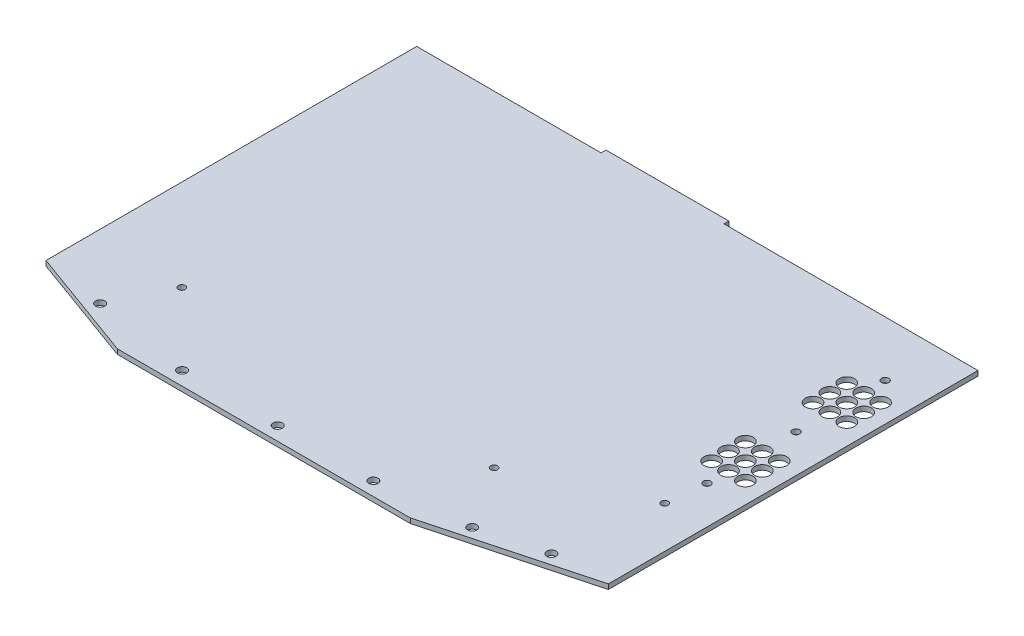
SolidWorks part; units mm, degrees
material "6061-T6 (SS)"
ref_plane "X-Y Datum" through (0, 0, 0) normal (0, 0, 1) x (1, 0, 0)
ref_plane "X-Z Datum" through (0, 0, 0) normal (0, 1, 0) x (1, 0, 0)
ref_plane "Y-Z Datum" through (0, 0, 0) normal (1, 0, 0) x (0, 0, -1)
sketch "Sketch1" plane through (0, 0, 0) normal (0, 0, 1) x (1, 0, 0)
  line L1 (-154.0408, -1.5875) -> (154.0408, -1.5875)
  line L2 (-154.0408, -1.5875) -> (-154.0408, 1.5875)
  line L3 (-154.0408, 1.5875) -> (154.0408, 1.5875)
  line L4 (154.0408, -1.5875) -> (154.0408, 1.5875)
  line L5 (-154.0408, -1.5875) -> (154.0408, 1.5875) construction
  line L6 (-154.0408, 1.5875) -> (154.0408, -1.5875) construction
  point P0 (0, 0)
  dimension "D1" = 3.175
  dimension "D2" = 308.0817
extrude "Boss-Extrude1" add sketch "Sketch1" along normal blind 267.83
sketch "Sketch3" plane through (154.0408, 0, 0) normal (1, 0, 0) x (0, 0, -1)
  line L9 (0, -1.5875) -> (0, 1.5875)
  line L10 (0, 1.5875) -> (-267.83, 1.5875)
  line L11 (-267.83, 1.5875) -> (-267.83, -1.5875)
  line L12 (-267.83, -1.5875) -> (0, -1.5875)
  line L13 (0, -1.5875) -> (0, 1.5875)
  line L14 (0, 1.5875) -> (-267.83, 1.5875)
  line L15 (-267.83, 1.5875) -> (-267.83, -1.5875)
  line L16 (-267.83, -1.5875) -> (0, -1.5875)
  dimension "D1" = 0
extrude "Boss-Extrude3" add sketch "Sketch3" along normal blind 3.175
sketch "Sketch4" plane through (0, 0, 267.83) normal (0, 0, 1) x (1, 0, 0)
  line L1 (157.2158, -1.5875) -> (208.1047, -1.5875)
  line L2 (157.2158, -1.5875) -> (157.2158, 1.5875)
  line L3 (157.2158, 1.5875) -> (208.1047, 1.5875)
  line L4 (208.1047, -1.5875) -> (208.1047, 1.5875)
  dimension "D1" = 3.175
  dimension "D2" = 50.8889
extrude "Boss-Extrude4" add sketch "Sketch4" against normal blind 267.83
sketch "Sketch6" plane through (0, 1.5875, 0) normal (0, 1, 0) x (1, 0, 0)
  line L0 (106.5047, -267.83) -> (106.5047, -223.38)
  line L1 (208.1047, -267.83) -> (-154.0408, -267.83) construction
  line L2 (208.1047, -223.38) -> (106.5047, -223.38)
  line L3 (208.1047, 0) -> (208.1047, -267.83) construction
  line L5 (106.5047, -267.83) -> (208.1047, -240.6064)
  line L7 (-154.0408, -267.83) -> (208.1047, -267.83) construction
  line L8 (208.1047, 0) -> (208.1047, -267.83) construction
  line L9 (208.1047, 0) -> (208.1047, -267.83)
  point P12 (208.1047, -240.6064)
  point P14 (208.1043, -240.6015)
  line M9 (-154.0408, -267.83) -> (208.1047, -267.83)
  line M10 (208.1047, -267.83) -> (208.1047, 0)
  dimension "D1" = 44.45
  dimension "D2" = 101.6
  dimension "D3" = 15
extrude "Cut-Extrude1" cut sketch "Sketch6" against normal through all contours L5 M9 M10 region at (174.2381, 1.5875, 258.7555)
sketch "Sketch11" plane through (0, -1.5875, 0) normal (0, -1, 0) x (1, 0, 0)
  line L0 (-84.1908, 267.83) -> (-84.1908, 242.43)
  line L1 (-154.0408, 267.83) -> (106.5047, 267.83) construction
  line L2 (-154.0408, 242.43) -> (-84.1908, 242.43)
  line L3 (-154.0408, 267.83) -> (-154.0408, 0) construction
  line L4 (-154.0408, 242.43) -> (-84.1908, 267.83)
  line M4 (-154.0408, 267.83) -> (-154.0408, 0)
  line M18 (106.5047, 267.83) -> (-154.0408, 267.83)
  dimension "D1" = 69.85
  dimension "D2" = 25.4
extrude "Cut-Extrude3" cut sketch "Sketch11" against normal through all contours L4 M4 M18 region at (-130.7575, -1.5875, 259.3633)
sketch "Sketch17" plane through (-154.0408, 0, 0) normal (-1, 0, 0) x (0, 0, 1)
  line L16 (0, -1.5875) -> (242.43, -1.5875)
  line L17 (242.43, -1.5875) -> (242.43, 1.5875)
  line L18 (242.43, 1.5875) -> (0, 1.5875)
  line L19 (0, 1.5875) -> (0, -1.5875)
  line L20 (0, -1.5875) -> (242.43, -1.5875)
  line L21 (242.43, -1.5875) -> (242.43, 1.5875)
  line L22 (242.43, 1.5875) -> (0, 1.5875)
  line L23 (0, 1.5875) -> (0, -1.5875)
  dimension "D1" = 0
extrude "Boss-Extrude5" add sketch "Sketch17" along normal blind 3.175
sketch "Sketch23" plane through (0, 1.5875, 0) normal (0, 1, 0) x (1, 0, 0)
  line L0 (-154.0408, -242.43) -> (-157.2158, -241.2755)
  line L2 (-154.0408, -242.43) -> (-84.1908, -267.83) construction
  line L3 (-154.0408, -242.43) -> (-84.1908, -267.83) construction
  line L4 (-157.2158, 0) -> (-157.2158, -242.43) construction
  point P2 (0, 0)
  point P3 (-156.4627, -241.5493)
  point P10 (-154.0408, -242.43)
extrude "Cut-Extrude7" cut sketch "Sketch23" against normal through all and the other way through all
sketch "Sketch25" plane through (0, -1.5875, 0) normal (0, -1, 0) x (1, 0, 0)
  line L0 (-157.2289, 241.2707) -> (-83.9953, 267.9011) construction
  line L1 (-50.9753, 267.83) -> (-50.9753, 258.94)
  line L2 (-157.2158, 241.2755) -> (-84.1908, 267.83) construction
  line L3 (-118.0827, 255.5057) -> (-115.3206, 247.91)
  line L5 (-84.1908, 267.83) -> (106.5047, 267.83) construction
  line L6 (-50.9753, 258.94) -> (11.2547, 258.94) construction
  line L7 (11.2547, 258.94) -> (73.4847, 258.94) construction
  line L8 (172.3981, 250.1739) -> (172.5447, 242.093)
  line L9 (106.5047, 267.83) -> (208.1047, 240.6064) construction
  line L10 (172.5447, 242.093) -> (131.9047, 252.9824) construction
  circle A0 centre (-115.3206, 247.91) radius 3
  circle A1 centre (-50.9753, 258.94) radius 3
  circle A2 centre (11.2547, 258.94) radius 3
  circle A3 centre (73.4847, 258.94) radius 3
  circle A4 centre (172.5447, 242.093) radius 3
  circle A5 centre (131.9047, 252.9824) radius 3
  dimension "D2" = 90
  dimension "D3" = 6
  dimension "D13" = 8.89
  dimension "D1" = 8.0823
  dimension "D5" = 33.02
  dimension "D6" = 62.23
  dimension "D7" = 62.23
  dimension "D8" = 33.02
  dimension "D9" = 35.56
  dimension "D10" = 73.96
  dimension "D11" = 40.64
  dimension "D12" = 8.0823
extrude "Cut-Extrude8" cut sketch "Sketch25" against normal blind 3.175 contours A0 | A1 | A2 | A5 | A4 | A3 region at (-116.993, -1.5875, 245.5223) region at (-53.0366, -1.5875, 256.8787) region at (11.2547, -1.5875, 258.94) region at (170.5022, -1.5875, 240.013) region at (131.9047, -1.5875, 252.9824)
sketch "Sketch27" plane through (0, -1.5875, 0) normal (0, -1, 0) x (1, 0, 0)
  circle A0 centre (172.4867, 137.7748) radius 5 construction
  circle A1 centre (172.4867, 137.7748) radius 5
  circle A2 centre (183.4867, 137.7748) radius 5 construction
  circle A3 centre (183.4867, 137.7748) radius 5
  circle A4 centre (194.4867, 137.7748) radius 5 construction
  circle A5 centre (194.4867, 126.7748) radius 5 construction
  circle A6 centre (194.4867, 115.7748) radius 5 construction
  circle A7 centre (183.4867, 126.7748) radius 5 construction
  circle A8 centre (183.4867, 115.7748) radius 5 construction
  circle A9 centre (172.4867, 115.7748) radius 5 construction
  circle A10 centre (172.4867, 126.7748) radius 5 construction
  circle A11 centre (194.4867, 137.7748) radius 5
  circle A12 centre (194.4867, 126.7748) radius 5
  circle A13 centre (194.4867, 115.7748) radius 5
  circle A14 centre (183.4867, 126.7748) radius 5
  circle A15 centre (183.4867, 115.7748) radius 5
  circle A16 centre (172.4867, 115.7748) radius 5
  circle A17 centre (172.4867, 126.7748) radius 5
  circle A18 centre (194.4867, 71.7748) radius 5 construction
  circle A19 centre (194.4867, 60.7748) radius 5 construction
  circle A20 centre (194.4867, 49.7748) radius 5 construction
  circle A21 centre (183.4867, 71.7748) radius 5 construction
  circle A22 centre (183.4867, 60.7748) radius 5 construction
  circle A23 centre (183.4867, 49.7748) radius 5 construction
  circle A24 centre (172.4867, 49.7748) radius 5 construction
  circle A25 centre (172.4867, 60.7748) radius 5 construction
  circle A26 centre (172.4867, 71.7748) radius 5 construction
  circle A27 centre (194.4867, 71.7748) radius 5
  circle A28 centre (194.4867, 60.7748) radius 5
  circle A29 centre (194.4867, 49.7748) radius 5
  circle A30 centre (183.4867, 71.7748) radius 5
  circle A31 centre (183.4867, 60.7748) radius 5
  circle A32 centre (183.4867, 49.7748) radius 5
  circle A33 centre (172.4867, 49.7748) radius 5
  circle A34 centre (172.4867, 60.7748) radius 5
  circle A35 centre (172.4867, 71.7748) radius 5
extrude "Cut-Extrude9" cut sketch "Sketch27" against normal through all
sketch "Sketch28" plane through (0, -1.5875, 0) normal (0, -1, 0) x (1, 0, 0)
  point P1 (105.429, 212.285)
  point P3 (-97.7709, 212.285)
  point P10 (180.965, 176.776)
hole_wizard "M4 Clearance Hole1" positions "Sketch28" profile "Sketch29" hole size "M4" standard "ANSI Metric" end condition through all
sketch "Sketch29" plane through (105.429, -1.5875, 212.285) normal (1, 0, 0) x (0, 0, -1)
  line L0 (0, 0) -> (0, 3.175)
  line L1 (0, 3.175) -> (2.25, 3.175)
  line L2 (2.25, 3.175) -> (2.25, 0)
  line L5 (2.25, 0) -> (0, 0)
  line L11 (0, -6.35) -> (0, 107.95) construction
  dimension "Thru Hole Dia." = 4.5
  dimension "Thru Hole Depth" = 3.175
sketch "Sketch30" plane through (0, 0, 0) normal (0, 0, -1) x (-1, 0, 0)
  line L0 (37.216, 1.5875) -> (37.216, -1.5875) construction
  line L1 (-42.784, 1.5875) -> (37.216, 1.5875) construction
  line L2 (-42.784, 1.5875) -> (-42.784, -1.5875) construction
  line L3 (37.216, 1.5875) -> (37.216, -1.5875)
  line L4 (-42.784, 1.5875) -> (37.216, 1.5875)
  line L5 (-42.784, 1.5875) -> (-42.784, -1.5875)
  line L6 (157.2158, -1.5875) -> (-208.1047, -1.5875) construction
  line L7 (157.2158, -1.5875) -> (-208.1047, -1.5875)
  line M1 (157.2158, 1.5875) -> (-208.1047, 1.5875)
  line M3 (-208.1047, -1.5875) -> (157.2158, -1.5875)
extrude "Boss-Extrude6" add sketch "Sketch30" along normal blind 3.175 contours L5 L3 M1 M3 region at (2.784, 0, 0)
sketch "Sketch31" plane through (0, -1.5875, 0) normal (0, -1, 0) x (1, 0, 0)
  circle A0 centre (183.4867, 151.7748) radius 2.4 construction
  circle A1 centre (183.4867, 151.7748) radius 2.4
extrude "Cut-Extrude10" cut sketch "Sketch31" against normal through all both and the other way through all
pattern_linear "LPattern1" count 3 spacing 58 along (0, 0, -1) of "Cut-Extrude10"
